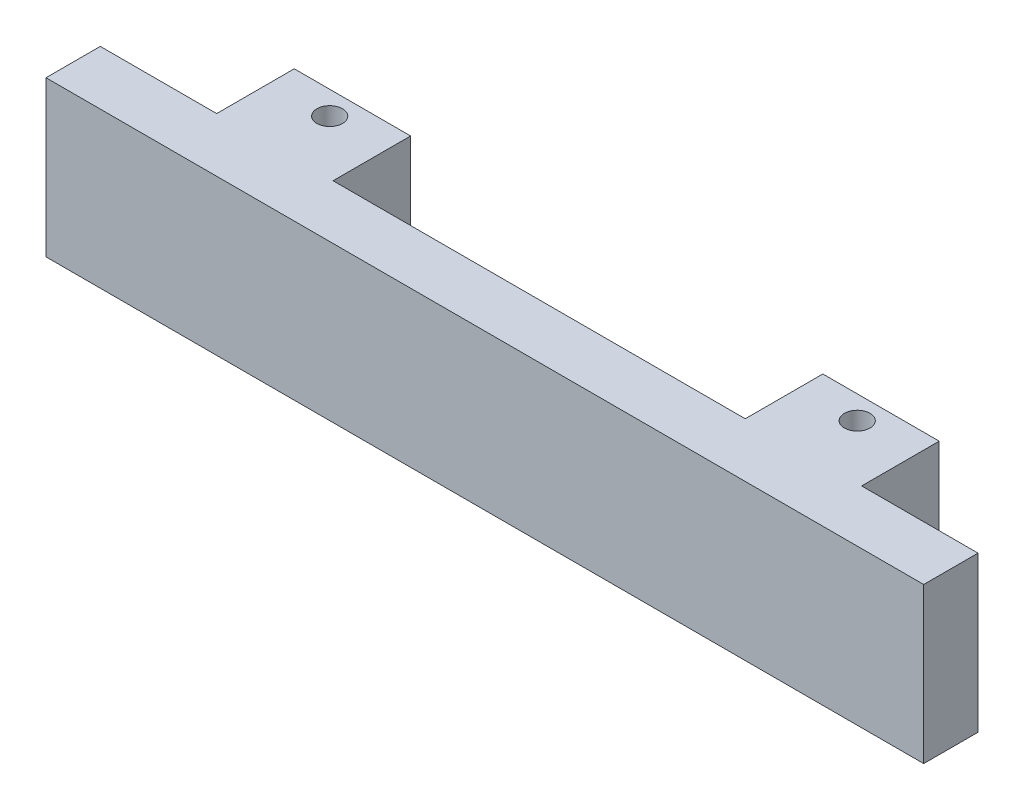
SolidWorks part; units mm, degrees
material "6061 合金"
ref_plane "前视基准面" through (0, 0, 0) normal (0, 0, 1) x (1, 0, 0)
ref_plane "上视基准面" through (0, 0, 0) normal (0, 1, 0) x (1, 0, 0)
ref_plane "右视基准面" through (0, 0, 0) normal (1, 0, 0) x (0, 0, -1)
sketch "草图1" plane through (0, 0, 0) normal (1, 0, 0) x (0, 0, -1)
  line L1 (-3.5, -10) -> (3.5, -10)
  line L2 (-3.5, -10) -> (-3.5, 10)
  line L3 (-3.5, 10) -> (3.5, 10)
  line L4 (3.5, -10) -> (3.5, 10)
  line L5 (-3.5, -10) -> (3.5, 10) construction
  line L6 (-3.5, 10) -> (3.5, -10) construction
  point P0 (0, 0)
  dimension "D1" = 7
  dimension "D2" = 20
extrude "凸台-拉伸1" add sketch "草图1" along normal mid plane 113.14
sketch "草图2" plane through (0, 0, -3.5) normal (0, 0, -1) x (-1, 0, 0)
  line L0 (-56.57, 10) -> (56.57, 10) construction
  line L1 (-26.57, -2) -> (-41.57, -2)
  line L2 (-26.57, -2) -> (-26.57, 10)
  line L3 (-26.57, 10) -> (-41.57, 10)
  line L4 (-41.57, -2) -> (-41.57, 10)
  line L5 (-26.57, -2) -> (-41.57, 10) construction
  line L6 (-26.57, 10) -> (-41.57, -2) construction
  line L7 (-56.57, -10) -> (56.57, -10) construction
  line L8 (-56.57, -10) -> (-56.57, 10) construction
  line L9 (0, 0) -> (0, 27.5606) construction
  point P0 (-34.07, 4)
  dimension "D1" = 8
  dimension "D2" = 15
  dimension "D3" = 15
extrude "凸台-拉伸2" add sketch "草图2" along normal blind 10
mirror "镜向1" about plane through (0, 0, 0) normal (1, 0, 0) of "凸台-拉伸2"
hole_wizard "M4 螺纹孔1" positions "草图4" profile "草图3" tap size "M4" standard "GB" end condition up to next
sketch "草图4" plane through (0, -2, 0) normal (0, -1, 0) x (-1, 0, 0)
  line L0 (0, 0) -> (0, 24.8691) construction
  line L1 (41.57, 13.5) -> (26.57, 13.5) construction
  point P6 (34, 10.5)
  point P8 (-34, 10.5)
  dimension "D1" = 3
  dimension "D2" = 68
sketch "草图3" plane through (-34, -2, -10.5) normal (1, 0, 0) x (0, 0, -1)
  line L0 (0, 0) -> (0, 12)
  line L1 (0, 12) -> (1.65, 12)
  line L2 (1.65, 12) -> (1.65, 0)
  line L5 (1.65, 0) -> (0, 0)
  line L11 (0, -6.35) -> (0, 107.95) construction
  dimension "通孔螺纹孔钻头直径" = 3.3
  dimension "通孔螺纹孔钻头深度" = 12
cosmetic thread "孔螺蚊线1" parameters "D2"=4
cosmetic thread "孔螺蚊线2" parameters "D2"=4
